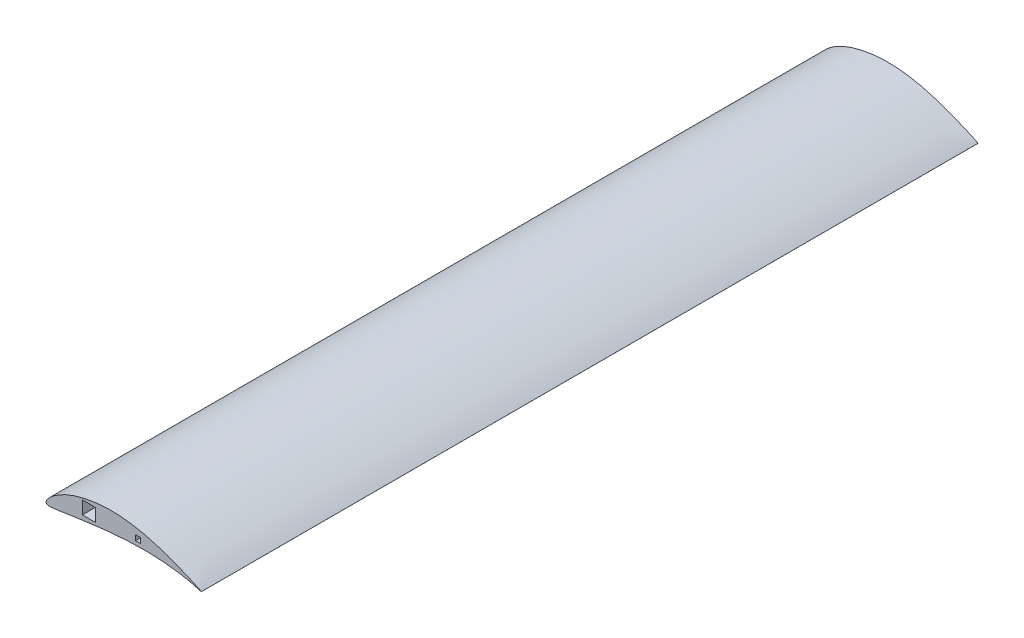
SolidWorks part; units mm, degrees
ref_plane "Front Plane" through (0, 0, 0) normal (0, 0, 1) x (1, 0, 0)
ref_plane "Top Plane" through (0, 0, 0) normal (0, 1, 0) x (1, 0, 0)
ref_plane "Right Plane" through (0, 0, 0) normal (1, 0, 0) x (0, 0, -1)
curve "Curve1"
  spline degree 3 poles (1.0002, -0.0023, 0) (1, 0, 0) (1.0002, 0.0023, 0) (0.9919, 0.0001, 0) (0.9849, 0.0027, 0) (0.9729, 0.003, 0) (0.9609, 0.0043, 0) (0.9483, 0.0054, 0) (0.9357, 0.0065, 0) (0.9231, 0.0077, 0) (0.9104, 0.0088, 0) (0.8978, 0.01, 0) (0.8852, 0.0111, 0) (0.8725, 0.0123, 0) (0.8599, 0.0134, 0) (0.8473, 0.0146, 0) (0.8347, 0.0157, 0) (0.8221, 0.0168, 0) (0.8094, 0.0179, 0) (0.7968, 0.019, 0) (0.7842, 0.0201, 0) (0.7716, 0.0211, 0) (0.759, 0.0222, 0) (0.7464, 0.0232, 0) (0.7337, 0.0243, 0) (0.7211, 0.0253, 0) (0.7085, 0.0263, 0) (0.6959, 0.0273, 0) (0.6833, 0.0283, 0) (0.6706, 0.0293, 0) (0.658, 0.0303, 0) (0.6454, 0.0313, 0) (0.6328, 0.0322, 0) (0.6202, 0.0331, 0) (0.6076, 0.0341, 0) (0.595, 0.035, 0) (0.5823, 0.0358, 0) (0.5697, 0.0367, 0) (0.5571, 0.0375, 0) (0.5446, 0.0384, 0) (0.532, 0.0392, 0) (0.5194, 0.0399, 0) (0.5068, 0.0407, 0) (0.4942, 0.0414, 0) (0.4816, 0.0421, 0) (0.469, 0.0427, 0) (0.4565, 0.0434, 0) (0.4439, 0.044, 0) (0.4313, 0.0445, 0) (0.4188, 0.0451, 0) (0.4062, 0.0456, 0) (0.3936, 0.046, 0) (0.3811, 0.0464, 0) (0.3685, 0.0468, 0) (0.356, 0.0472, 0) (0.3435, 0.0475, 0) (0.3309, 0.0477, 0) (0.3184, 0.0479, 0) (0.3059, 0.0481, 0) (0.2934, 0.0482, 0) (0.2809, 0.0482, 0) (0.2685, 0.0482, 0) (0.256, 0.0481, 0) (0.2436, 0.0479, 0) (0.2312, 0.0477, 0) (0.2189, 0.0474, 0) (0.2065, 0.047, 0) (0.1942, 0.0465, 0) (0.182, 0.0459, 0) (0.1698, 0.0452, 0) (0.1576, 0.0444, 0) (0.1456, 0.0434, 0) (0.1336, 0.0423, 0) (0.1217, 0.0411, 0) (0.1099, 0.0397, 0) (0.0983, 0.038, 0) (0.0868, 0.0362, 0) (0.0756, 0.0342, 0) (0.0647, 0.0319, 0) (0.0541, 0.0294, 0) (0.0441, 0.0266, 0) (0.0348, 0.0236, 0) (0.0266, 0.0205, 0) (0.0197, 0.0175, 0) (0.0142, 0.0146, 0) (0.0101, 0.012, 0) (0.007, 0.0098, 0) (0.0047, 0.0078, 0) (0.003, 0.006, 0) (0.0018, 0.0045, 0) (0.0009, 0.003, 0) (0.0003, 0.0017, 0) (0, 0.0004, 0) (0, -0.0008, 0) (0.0005, -0.0021, 0) (0.0015, -0.0032, 0) (0.0028, -0.0043, 0) (0.0046, -0.0054, 0) (0.0068, -0.0066, 0) (0.0097, -0.0078, 0) (0.0135, -0.0091, 0) (0.0186, -0.0106, 0) (0.0252, -0.0121, 0) (0.0334, -0.0135, 0) (0.043, -0.0148, 0) (0.0536, -0.0159, 0) (0.0648, -0.0167, 0) (0.0764, -0.0173, 0) (0.0882, -0.0177, 0) (0.1003, -0.018, 0) (0.1125, -0.0182, 0) (0.1247, -0.0183, 0) (0.1371, -0.0183, 0) (0.1495, -0.0182, 0) (0.162, -0.0181, 0) (0.1745, -0.0179, 0) (0.187, -0.0176, 0) (0.1996, -0.0174, 0) (0.2122, -0.0171, 0) (0.2248, -0.0167, 0) (0.2375, -0.0164, 0) (0.2501, -0.016, 0) (0.2628, -0.0156, 0) (0.2755, -0.0152, 0) (0.2882, -0.0147, 0) (0.3009, -0.0143, 0) (0.3136, -0.0139, 0) (0.3263, -0.0134, 0) (0.339, -0.0129, 0) (0.3517, -0.0125, 0) (0.3644, -0.012, 0) (0.3771, -0.0116, 0) (0.3897, -0.0111, 0) (0.4024, -0.0106, 0) (0.4151, -0.0102, 0) (0.4277, -0.0098, 0) (0.4404, -0.0093, 0) (0.4531, -0.0089, 0) (0.4657, -0.0085, 0) (0.4784, -0.0081, 0) (0.4911, -0.0077, 0) (0.5037, -0.0073, 0) (0.5164, -0.0069, 0) (0.5291, -0.0066, 0) (0.5417, -0.0062, 0) (0.5544, -0.0059, 0) (0.5671, -0.0055, 0) (0.5798, -0.0052, 0) (0.5924, -0.0049, 0) (0.6051, -0.0046, 0) (0.6178, -0.0044, 0) (0.6304, -0.0041, 0) (0.6431, -0.0039, 0) (0.6558, -0.0036, 0) (0.6685, -0.0034, 0) (0.6811, -0.0032, 0) (0.6938, -0.003, 0) (0.7065, -0.0029, 0) (0.7192, -0.0027, 0) (0.7318, -0.0026, 0) (0.7445, -0.0024, 0) (0.7572, -0.0023, 0) (0.7699, -0.0022, 0) (0.7826, -0.0021, 0) (0.7953, -0.002, 0) (0.8079, -0.0019, 0) (0.8206, -0.0019, 0) (0.8333, -0.0018, 0) (0.846, -0.0017, 0) (0.8588, -0.0017, 0) (0.8715, -0.0016, 0) (0.8842, -0.0015, 0) (0.8969, -0.0015, 0) (0.9096, -0.0014, 0) (0.9223, -0.0013, 0) (0.935, -0.0012, 0) (0.9477, -0.0011, 0) (0.9604, -0.0011, 0) (0.9725, -0.0007, 0) (0.9848, -0.0014, 0) (0.9918, 0.0007, 0) (1.0002, -0.0023, 0) (1, 0, 0) (1.0002, 0.0023, 0) knots -0.007874 -0.002894 -0.000332 0 0.000332 0.002885 0.007815 0.013623 0.01978 0.026037 0.032316 0.038604 0.044895 0.051184 0.057469 0.06375 0.070028 0.076304 0.082578 0.088851 0.095124 0.101396 0.107668 0.113941 0.120213 0.126487 0.132762 0.139036 0.145311 0.151585 0.157859 0.16413 0.170401 0.17667 0.182937 0.189202 0.195466 0.201728 0.207987 0.214245 0.2205 0.226754 0.233005 0.239253 0.2455 0.251744 0.257986 0.264226 0.270464 0.2767 0.282933 0.289165 0.295394 0.30162 0.307843 0.314063 0.32028 0.326491 0.332699 0.3389 0.345096 0.351285 0.357467 0.363641 0.369805 0.375959 0.382101 0.38823 0.394345 0.400443 0.406521 0.412577 0.418607 0.424607 0.430573 0.436498 0.442374 0.448192 0.453938 0.459595 0.465142 0.470542 0.475738 0.480625 0.48504 0.488808 0.491844 0.494208 0.496047 0.497501 0.498679 0.499657 0.500486 0.501199 0.501823 0.502412 0.503041 0.50376 0.504602 0.505602 0.50682 0.508337 0.510284 0.512841 0.516185 0.520365 0.525232 0.530552 0.536146 0.541914 0.547804 0.553781 0.559821 0.565909 0.57203 0.578179 0.584352 0.590546 0.596759 0.60299 0.609237 0.615497 0.621768 0.62805 0.634339 0.640634 0.646932 0.653231 0.659529 0.665824 0.672115 0.678404 0.684692 0.690977 0.69726 0.703542 0.709822 0.716099 0.722375 0.728651 0.734927 0.741206 0.747487 0.753768 0.76005 0.766331 0.772611 0.778892 0.785172 0.791451 0.79773 0.804009 0.810289 0.816569 0.822848 0.829126 0.835406 0.841685 0.847965 0.854245 0.860527 0.866808 0.87309 0.879373 0.885657 0.891942 0.898228 0.904515 0.910804 0.917095 0.923389 0.929686 0.935986 0.942288 0.948588 0.954885 0.961183 0.96748 0.973774 0.980051 0.986247 0.992126 0.997106 0.999668 1 1.000332 1.002885 1.007815 periodic
curve "Curve6"
  spline degree 3 poles (0, 0, 0) (0.0002, 0.0017, 0) (0.0007, 0.0052, 0) (0.0046, 0.01, 0) (0.01, 0.0151, 0) (0.0174, 0.0207, 0) (0.027, 0.0264, 0) (0.0385, 0.0321, 0) (0.052, 0.0379, 0) (0.0675, 0.0434, 0) (0.0847, 0.0488, 0) (0.1038, 0.0538, 0) (0.1245, 0.0586, 0) (0.1469, 0.063, 0) (0.1707, 0.0671, 0) (0.196, 0.0706, 0) (0.2226, 0.0737, 0) (0.2503, 0.0762, 0) (0.2792, 0.0783, 0) (0.3089, 0.0796, 0) (0.3395, 0.0805, 0) (0.3708, 0.0807, 0) (0.4026, 0.0805, 0) (0.4348, 0.0796, 0) (0.4674, 0.0782, 0) (0.5, 0.0763, 0) (0.5327, 0.074, 0) (0.5652, 0.0714, 0) (0.5974, 0.0683, 0) (0.6292, 0.0649, 0) (0.6605, 0.0611, 0) (0.6911, 0.057, 0) (0.7209, 0.0527, 0) (0.7497, 0.0482, 0) (0.7774, 0.0435, 0) (0.804, 0.0388, 0) (0.8292, 0.0342, 0) (0.8531, 0.0298, 0) (0.8754, 0.0255, 0) (0.8961, 0.0215, 0) (0.9151, 0.0177, 0) (0.9324, 0.0142, 0) (0.9478, 0.0111, 0) (0.9613, 0.0083, 0) (0.9728, 0.0059, 0) (0.9823, 0.0039, 0) (0.9897, 0.0023, 0) (0.9949, 0.0006, 0) (0.9983, 0.0007, 0) (0.9996, 0.0001, 0) (1, 0, 0) knots 0 0 0 0 0.004816 0.010311 0.017533 0.026619 0.037456 0.050036 0.064348 0.080358 0.098009 0.117234 0.138018 0.160262 0.183891 0.2088 0.234911 0.262128 0.290345 0.319442 0.34932 0.379858 0.410934 0.442439 0.474224 0.506171 0.538142 0.570006 0.601639 0.632894 0.663653 0.693783 0.723155 0.751647 0.779129 0.805464 0.830536 0.854232 0.876442 0.897072 0.916014 0.933209 0.948567 0.962012 0.9735 0.982962 0.990398 0.99574 0.998893 1 1 1 1
curve "Curve7"
  spline degree 3 poles (0.0009, -0.0041, 0) (-0.0004, 0.0004, 0) (0.0009, 0.0052, 0) (0.0045, 0.01, 0) (0.01, 0.0151, 0) (0.0174, 0.0207, 0) (0.027, 0.0264, 0) (0.0385, 0.0321, 0) (0.052, 0.0379, 0) (0.0675, 0.0434, 0) (0.0847, 0.0488, 0) (0.1038, 0.0538, 0) (0.1245, 0.0586, 0) (0.1469, 0.063, 0) (0.1707, 0.0671, 0) (0.196, 0.0706, 0) (0.2226, 0.0737, 0) (0.2503, 0.0762, 0) (0.2792, 0.0783, 0) (0.3089, 0.0796, 0) (0.3395, 0.0805, 0) (0.3708, 0.0807, 0) (0.4026, 0.0805, 0) (0.4348, 0.0796, 0) (0.4674, 0.0782, 0) (0.5, 0.0763, 0) (0.5327, 0.074, 0) (0.5652, 0.0714, 0) (0.5974, 0.0683, 0) (0.6292, 0.0649, 0) (0.6605, 0.0611, 0) (0.6911, 0.057, 0) (0.7209, 0.0527, 0) (0.7497, 0.0482, 0) (0.7774, 0.0435, 0) (0.804, 0.0388, 0) (0.8292, 0.0342, 0) (0.8531, 0.0298, 0) (0.8754, 0.0255, 0) (0.8961, 0.0215, 0) (0.9151, 0.0177, 0) (0.9324, 0.0142, 0) (0.9478, 0.0111, 0) (0.9613, 0.0083, 0) (0.9728, 0.0059, 0) (0.9823, 0.0038, 0) (0.9896, 0.0024, 0) (0.9953, 0.0005, 0) (0.9978, 0.0008, 0) (1.0006, -0.0001, 0) (0.9977, 0.0003, 0) (0.9953, 0, 0) (0.9896, 0.0009, 0) (0.9823, 0.0014, 0) (0.9728, 0.0025, 0) (0.9613, 0.0036, 0) (0.9478, 0.0048, 0) (0.9324, 0.006, 0) (0.9151, 0.0072, 0) (0.8961, 0.0083, 0) (0.8754, 0.0093, 0) (0.8531, 0.0102, 0) (0.8292, 0.0108, 0) (0.8039, 0.0112, 0) (0.7774, 0.0112, 0) (0.7496, 0.0109, 0) (0.7208, 0.0102, 0) (0.6911, 0.0092, 0) (0.6605, 0.0079, 0) (0.6292, 0.0062, 0) (0.5974, 0.004, 0) (0.5652, 0.0016, 0) (0.5326, -0.0011, 0) (0.5, -0.0039, 0) (0.4673, -0.0069, 0) (0.4348, -0.0098, 0) (0.4026, -0.0128, 0) (0.3708, -0.0154, 0) (0.3395, -0.018, 0) (0.3089, -0.0201, 0) (0.2792, -0.022, 0) (0.2504, -0.0233, 0) (0.2226, -0.0244, 0) (0.1961, -0.0249, 0) (0.1708, -0.0253, 0) (0.147, -0.0252, 0) (0.1246, -0.0248, 0) (0.1039, -0.024, 0) (0.0848, -0.023, 0) (0.0676, -0.0217, 0) (0.0522, -0.0201, 0) (0.0387, -0.0182, 0) (0.0271, -0.0161, 0) (0.0176, -0.0135, 0) (0.01, -0.0109, 0) (0.0046, -0.0077, 0) (0.0009, -0.0041, 0) (-0.0004, 0.0004, 0) (0.0009, 0.0052, 0) knots -0.007287 -0.004212 -0.00188 0 0.002428 0.005198 0.00884 0.013421 0.018885 0.025227 0.032443 0.040515 0.049414 0.059107 0.069586 0.080801 0.092714 0.105273 0.118437 0.13216 0.146386 0.161056 0.17612 0.191517 0.207184 0.223068 0.239094 0.255201 0.27132 0.287385 0.303334 0.319092 0.3346 0.349791 0.364599 0.378965 0.392821 0.406098 0.418739 0.430686 0.441884 0.452285 0.461835 0.470504 0.478247 0.485026 0.490819 0.495589 0.499338 0.502031 0.503621 0.504179 0.504707 0.506286 0.508919 0.512589 0.517281 0.522978 0.529643 0.537254 0.545772 0.555157 0.565377 0.576386 0.588132 0.60057 0.613645 0.627312 0.641507 0.656169 0.671241 0.686661 0.702362 0.718285 0.734352 0.750492 0.766637 0.782713 0.798656 0.81438 0.829825 0.844919 0.8596 0.873808 0.887483 0.900562 0.912999 0.924742 0.935744 0.94596 0.955342 0.963865 0.971494 0.978201 0.983972 0.988807 0.992713 0.995788 0.99812 1 1.002428 1.005198 1.00884 periodic
curve "Curve8"
  spline degree 3 poles (1, 0.0001, 0) (0.9992, 0.0006, 0) (0.9962, 0.0026, 0) (0.9897, 0.0065, 0) (0.9795, 0.0117, 0) (0.966, 0.0177, 0) (0.9494, 0.025, 0) (0.9297, 0.0336, 0) (0.9068, 0.0433, 0) (0.8812, 0.0541, 0) (0.853, 0.0656, 0) (0.8225, 0.0776, 0) (0.79, 0.0897, 0) (0.7558, 0.1017, 0) (0.7202, 0.1132, 0) (0.6835, 0.1241, 0) (0.6459, 0.134, 0) (0.6078, 0.1427, 0) (0.5695, 0.1499, 0) (0.5311, 0.1556, 0) (0.4927, 0.1597, 0) (0.4545, 0.162, 0) (0.4165, 0.1627, 0) (0.3791, 0.1616, 0) (0.3423, 0.1589, 0) (0.3063, 0.1546, 0) (0.2715, 0.1489, 0) (0.2379, 0.1418, 0) (0.2058, 0.1335, 0) (0.1754, 0.124, 0) (0.1469, 0.1134, 0) (0.1204, 0.1018, 0) (0.0962, 0.0895, 0) (0.0744, 0.0767, 0) (0.0552, 0.0638, 0) (0.0386, 0.051, 0) (0.0247, 0.0387, 0) (0.0137, 0.027, 0) (0.0057, 0.0163, 0) (0.0011, 0.0075, 0) (-0.0003, 0.0005, 0) (0.0007, -0.0053, 0) (0.0058, -0.01, 0) (0.0142, -0.0123, 0) (0.0253, -0.0129, 0) (0.0391, -0.0122, 0) (0.0556, -0.0102, 0) (0.0748, -0.0075, 0) (0.0966, -0.0042, 0) (0.1207, -0.0007, 0) (0.1472, 0.0033, 0) (0.1757, 0.0076, 0) (0.206, 0.0121, 0) (0.2381, 0.0168, 0) (0.2716, 0.0215, 0) (0.3064, 0.0261, 0) (0.3423, 0.0305, 0) (0.3791, 0.0347, 0) (0.4165, 0.0385, 0) (0.4544, 0.0419, 0) (0.4926, 0.0448, 0) (0.531, 0.047, 0) (0.5694, 0.0486, 0) (0.6077, 0.0495, 0) (0.6458, 0.0495, 0) (0.6833, 0.0486, 0) (0.7201, 0.0469, 0) (0.7557, 0.0444, 0) (0.7899, 0.0412, 0) (0.8225, 0.0376, 0) (0.853, 0.0334, 0) (0.8812, 0.0289, 0) (0.9069, 0.0241, 0) (0.9297, 0.0193, 0) (0.9494, 0.0145, 0) (0.966, 0.0098, 0) (0.9793, 0.0054, 0) (0.9895, 0.0024, 0) (0.9961, 0.0007, 0) (0.9992, 0.0001, 0) (1, -0.0001, 0) knots 0 0 0 0 0.001413 0.005226 0.010781 0.017816 0.026461 0.036791 0.048686 0.062017 0.076639 0.092363 0.109003 0.126387 0.144339 0.162701 0.181313 0.200023 0.218713 0.237261 0.255692 0.274037 0.292193 0.310133 0.327788 0.345097 0.362002 0.378421 0.394287 0.409543 0.424114 0.437938 0.450942 0.463044 0.474154 0.484165 0.493024 0.500713 0.507126 0.51213 0.514904 0.517171 0.520262 0.524245 0.529498 0.536092 0.544061 0.553363 0.563905 0.575615 0.58842 0.602227 0.616944 0.632457 0.648676 0.665501 0.682818 0.700538 0.718564 0.736789 0.755151 0.773513 0.791878 0.810245 0.828489 0.846493 0.864125 0.881249 0.897725 0.913415 0.928184 0.941897 0.954411 0.965603 0.97535 0.983576 0.990285 0.995433 0.9988 1 1 1 1
sketch "Sketch3" plane through (0, 0, 0) normal (0, 0, 1) x (1, 0, 0)
  line L0 (0, 0) -> (50, 0) construction
  line L1 (0.2298, 0.0405) -> (0.2298, 0.0158) construction
  line L2 (0.1804, 0.0405) -> (0.2298, 0.0405)
  line L3 (0.1804, 0.0405) -> (0.1804, -0.0089)
  line L4 (0.1804, -0.0089) -> (0.2298, -0.0089)
  line L5 (0.2298, 0.0405) -> (0.2298, -0.0089)
  line L6 (0.4642, 0.0242) -> (0.4889, 0.0242)
  line L7 (0.4642, 0.0242) -> (0.4642, -0.0005)
  line L8 (0.4642, -0.0005) -> (0.4889, -0.0005)
  line L9 (0.4889, 0.0242) -> (0.4889, -0.0005)
  line L10 (0.2298, 0.0158) -> (0.2146, 0.0158) construction
  line L11 (0.2146, 0.0158) -> (0.2146, 0.0405) construction
  line L12 (0.2146, 0.0405) -> (0.2298, 0.0405) construction
  line L13 (0, 0) -> (500, 0) construction
  line L14 (0.1804, 0.0458) -> (0.1804, -0.0178) construction
  line L15 (0, 0) -> (0, -165.9812) construction
  line L16 (0, -165.9812) -> (300, -165.9812) construction
  line L17 (72.7802, 36.2202) -> (92.7802, 36.2202) construction
  line L18 (70.2802, 13.7202) -> (95.2802, 13.7202)
  line L19 (70.2802, 13.7202) -> (70.2802, 38.7202)
  line L20 (70.2802, 38.7202) -> (95.2802, 38.7202)
  line L21 (95.2802, 13.7202) -> (95.2802, 38.7202)
  line L22 (92.7802, 16.2202) -> (92.7802, 36.2202) construction
  line L23 (72.7802, 16.2202) -> (92.7802, 16.2202) construction
  line L24 (72.7802, 16.2202) -> (72.7802, 36.2202) construction
  line L25 (300, -0.018) -> (300, 0.015)
  line L26 (172.9506, 31.8748) -> (182.9506, 31.8748)
  line L27 (172.9506, 31.8748) -> (172.9506, 21.8748)
  line L28 (172.9506, 21.8748) -> (182.9506, 21.8748)
  line L29 (182.9506, 31.8748) -> (182.9506, 21.8748)
  spline S0 degree 3 poles (1.0002, -0.0023) (1, 0) (1.0002, 0.0023) (0.9919, 0.0001) (0.9849, 0.0027) (0.9729, 0.003) (0.9609, 0.0043) (0.9483, 0.0054) (0.9357, 0.0065) (0.9231, 0.0077) (0.9104, 0.0088) (0.8978, 0.01) (0.8852, 0.0111) (0.8725, 0.0123) (0.8599, 0.0134) (0.8473, 0.0146) (0.8347, 0.0157) (0.8221, 0.0168) (0.8094, 0.0179) (0.7968, 0.019) (0.7842, 0.0201) (0.7716, 0.0211) (0.759, 0.0222) (0.7464, 0.0232) (0.7337, 0.0243) (0.7211, 0.0253) (0.7085, 0.0263) (0.6959, 0.0273) (0.6833, 0.0283) (0.6706, 0.0293) (0.658, 0.0303) (0.6454, 0.0313) (0.6328, 0.0322) (0.6202, 0.0331) (0.6076, 0.0341) (0.595, 0.035) (0.5823, 0.0358) (0.5697, 0.0367) (0.5571, 0.0375) (0.5446, 0.0384) (0.532, 0.0392) (0.5194, 0.0399) (0.5068, 0.0407) (0.4942, 0.0414) (0.4816, 0.0421) (0.469, 0.0427) (0.4565, 0.0434) (0.4439, 0.044) (0.4313, 0.0445) (0.4188, 0.0451) (0.4062, 0.0456) (0.3936, 0.046) (0.3811, 0.0464) (0.3685, 0.0468) (0.356, 0.0472) (0.3435, 0.0475) (0.3309, 0.0477) (0.3184, 0.0479) (0.3059, 0.0481) (0.2934, 0.0482) (0.2809, 0.0482) (0.2685, 0.0482) (0.256, 0.0481) (0.2436, 0.0479) (0.2312, 0.0477) (0.2189, 0.0474) (0.2065, 0.047) (0.1942, 0.0465) (0.182, 0.0459) (0.1698, 0.0452) (0.1576, 0.0444) (0.1456, 0.0434) (0.1336, 0.0423) (0.1217, 0.0411) (0.1099, 0.0397) (0.0983, 0.038) (0.0868, 0.0362) (0.0756, 0.0342) (0.0647, 0.0319) (0.0541, 0.0294) (0.0441, 0.0266) (0.0348, 0.0236) (0.0266, 0.0205) (0.0197, 0.0175) (0.0142, 0.0146) (0.0101, 0.012) (0.007, 0.0098) (0.0047, 0.0078) (0.003, 0.006) (0.0018, 0.0045) (0.0009, 0.003) (0.0003, 0.0017) (0, 0.0004) (0, -0.0008) (0.0005, -0.0021) (0.0015, -0.0032) (0.0028, -0.0043) (0.0046, -0.0054) (0.0068, -0.0066) (0.0097, -0.0078) (0.0135, -0.0091) (0.0186, -0.0106) (0.0252, -0.0121) (0.0334, -0.0135) (0.043, -0.0148) (0.0536, -0.0159) (0.0648, -0.0167) (0.0764, -0.0173) (0.0882, -0.0177) (0.1003, -0.018) (0.1125, -0.0182) (0.1247, -0.0183) (0.1371, -0.0183) (0.1495, -0.0182) (0.162, -0.0181) (0.1745, -0.0179) (0.187, -0.0176) (0.1996, -0.0174) (0.2122, -0.0171) (0.2248, -0.0167) (0.2375, -0.0164) (0.2501, -0.016) (0.2628, -0.0156) (0.2755, -0.0152) (0.2882, -0.0147) (0.3009, -0.0143) (0.3136, -0.0139) (0.3263, -0.0134) (0.339, -0.0129) (0.3517, -0.0125) (0.3644, -0.012) (0.3771, -0.0116) (0.3897, -0.0111) (0.4024, -0.0106) (0.4151, -0.0102) (0.4277, -0.0098) (0.4404, -0.0093) (0.4531, -0.0089) (0.4657, -0.0085) (0.4784, -0.0081) (0.4911, -0.0077) (0.5037, -0.0073) (0.5164, -0.0069) (0.5291, -0.0066) (0.5417, -0.0062) (0.5544, -0.0059) (0.5671, -0.0055) (0.5798, -0.0052) (0.5924, -0.0049) (0.6051, -0.0046) (0.6178, -0.0044) (0.6304, -0.0041) (0.6431, -0.0039) (0.6558, -0.0036) (0.6685, -0.0034) (0.6811, -0.0032) (0.6938, -0.003) (0.7065, -0.0029) (0.7192, -0.0027) (0.7318, -0.0026) (0.7445, -0.0024) (0.7572, -0.0023) (0.7699, -0.0022) (0.7826, -0.0021) (0.7953, -0.002) (0.8079, -0.0019) (0.8206, -0.0019) (0.8333, -0.0018) (0.846, -0.0017) (0.8588, -0.0017) (0.8715, -0.0016) (0.8842, -0.0015) (0.8969, -0.0015) (0.9096, -0.0014) (0.9223, -0.0013) (0.935, -0.0012) (0.9477, -0.0011) (0.9604, -0.0011) (0.9725, -0.0007) (0.9848, -0.0014) (0.9918, 0.0007) (1.0002, -0.0023) (1, 0) (1.0002, 0.0023) knots -0.007874 -0.002894 -0.000332 0 0.000332 0.002885 0.007815 0.013623 0.01978 0.026037 0.032316 0.038604 0.044895 0.051184 0.057469 0.06375 0.070028 0.076304 0.082578 0.088851 0.095124 0.101396 0.107668 0.113941 0.120213 0.126487 0.132762 0.139036 0.145311 0.151585 0.157859 0.16413 0.170401 0.17667 0.182937 0.189202 0.195466 0.201728 0.207987 0.214245 0.2205 0.226754 0.233005 0.239253 0.2455 0.251744 0.257986 0.264226 0.270464 0.2767 0.282933 0.289165 0.295394 0.30162 0.307843 0.314063 0.32028 0.326491 0.332699 0.3389 0.345096 0.351285 0.357467 0.363641 0.369805 0.375959 0.382101 0.38823 0.394345 0.400443 0.406521 0.412577 0.418607 0.424607 0.430573 0.436498 0.442374 0.448192 0.453938 0.459595 0.465142 0.470542 0.475738 0.480625 0.48504 0.488808 0.491844 0.494208 0.496047 0.497501 0.498679 0.499657 0.500486 0.501199 0.501823 0.502412 0.503041 0.50376 0.504602 0.505602 0.50682 0.508337 0.510284 0.512841 0.516185 0.520365 0.525232 0.530552 0.536146 0.541914 0.547804 0.553781 0.559821 0.565909 0.57203 0.578179 0.584352 0.590546 0.596759 0.60299 0.609237 0.615497 0.621768 0.62805 0.634339 0.640634 0.646932 0.653231 0.659529 0.665824 0.672115 0.678404 0.684692 0.690977 0.69726 0.703542 0.709822 0.716099 0.722375 0.728651 0.734927 0.741206 0.747487 0.753768 0.76005 0.766331 0.772611 0.778892 0.785172 0.791451 0.79773 0.804009 0.810289 0.816569 0.822848 0.829126 0.835406 0.841685 0.847965 0.854245 0.860527 0.866808 0.87309 0.879373 0.885657 0.891942 0.898228 0.904515 0.910804 0.917095 0.923389 0.929686 0.935986 0.942288 0.948588 0.954885 0.961183 0.96748 0.973774 0.980051 0.986247 0.992126 0.997106 0.999668 1 1.000332 1.002885 1.007815 only from (1, 0) to (1, 0) construction
  spline S1 degree 3 poles (1.0002, -0.0023) (1, 0) (1.0002, 0.0023) (0.9919, 0.0001) (0.9849, 0.0027) (0.9729, 0.003) (0.9609, 0.0043) (0.9483, 0.0054) (0.9357, 0.0065) (0.9231, 0.0077) (0.9104, 0.0088) (0.8978, 0.01) (0.8852, 0.0111) (0.8725, 0.0123) (0.8599, 0.0134) (0.8473, 0.0146) (0.8347, 0.0157) (0.8221, 0.0168) (0.8094, 0.0179) (0.7968, 0.019) (0.7842, 0.0201) (0.7716, 0.0211) (0.759, 0.0222) (0.7464, 0.0232) (0.7337, 0.0243) (0.7211, 0.0253) (0.7085, 0.0263) (0.6959, 0.0273) (0.6833, 0.0283) (0.6706, 0.0293) (0.658, 0.0303) (0.6454, 0.0313) (0.6328, 0.0322) (0.6202, 0.0331) (0.6076, 0.0341) (0.595, 0.035) (0.5823, 0.0358) (0.5697, 0.0367) (0.5571, 0.0375) (0.5446, 0.0384) (0.532, 0.0392) (0.5194, 0.0399) (0.5068, 0.0407) (0.4942, 0.0414) (0.4816, 0.0421) (0.469, 0.0427) (0.4565, 0.0434) (0.4439, 0.044) (0.4313, 0.0445) (0.4188, 0.0451) (0.4062, 0.0456) (0.3936, 0.046) (0.3811, 0.0464) (0.3685, 0.0468) (0.356, 0.0472) (0.3435, 0.0475) (0.3309, 0.0477) (0.3184, 0.0479) (0.3059, 0.0481) (0.2934, 0.0482) (0.2809, 0.0482) (0.2685, 0.0482) (0.256, 0.0481) (0.2436, 0.0479) (0.2312, 0.0477) (0.2189, 0.0474) (0.2065, 0.047) (0.1942, 0.0465) (0.182, 0.0459) (0.1698, 0.0452) (0.1576, 0.0444) (0.1456, 0.0434) (0.1336, 0.0423) (0.1217, 0.0411) (0.1099, 0.0397) (0.0983, 0.038) (0.0868, 0.0362) (0.0756, 0.0342) (0.0647, 0.0319) (0.0541, 0.0294) (0.0441, 0.0266) (0.0348, 0.0236) (0.0266, 0.0205) (0.0197, 0.0175) (0.0142, 0.0146) (0.0101, 0.012) (0.007, 0.0098) (0.0047, 0.0078) (0.003, 0.006) (0.0018, 0.0045) (0.0009, 0.003) (0.0003, 0.0017) (0, 0.0004) (0, -0.0008) (0.0005, -0.0021) (0.0015, -0.0032) (0.0028, -0.0043) (0.0046, -0.0054) (0.0068, -0.0066) (0.0097, -0.0078) (0.0135, -0.0091) (0.0186, -0.0106) (0.0252, -0.0121) (0.0334, -0.0135) (0.043, -0.0148) (0.0536, -0.0159) (0.0648, -0.0167) (0.0764, -0.0173) (0.0882, -0.0177) (0.1003, -0.018) (0.1125, -0.0182) (0.1247, -0.0183) (0.1371, -0.0183) (0.1495, -0.0182) (0.162, -0.0181) (0.1745, -0.0179) (0.187, -0.0176) (0.1996, -0.0174) (0.2122, -0.0171) (0.2248, -0.0167) (0.2375, -0.0164) (0.2501, -0.016) (0.2628, -0.0156) (0.2755, -0.0152) (0.2882, -0.0147) (0.3009, -0.0143) (0.3136, -0.0139) (0.3263, -0.0134) (0.339, -0.0129) (0.3517, -0.0125) (0.3644, -0.012) (0.3771, -0.0116) (0.3897, -0.0111) (0.4024, -0.0106) (0.4151, -0.0102) (0.4277, -0.0098) (0.4404, -0.0093) (0.4531, -0.0089) (0.4657, -0.0085) (0.4784, -0.0081) (0.4911, -0.0077) (0.5037, -0.0073) (0.5164, -0.0069) (0.5291, -0.0066) (0.5417, -0.0062) (0.5544, -0.0059) (0.5671, -0.0055) (0.5798, -0.0052) (0.5924, -0.0049) (0.6051, -0.0046) (0.6178, -0.0044) (0.6304, -0.0041) (0.6431, -0.0039) (0.6558, -0.0036) (0.6685, -0.0034) (0.6811, -0.0032) (0.6938, -0.003) (0.7065, -0.0029) (0.7192, -0.0027) (0.7318, -0.0026) (0.7445, -0.0024) (0.7572, -0.0023) (0.7699, -0.0022) (0.7826, -0.0021) (0.7953, -0.002) (0.8079, -0.0019) (0.8206, -0.0019) (0.8333, -0.0018) (0.846, -0.0017) (0.8588, -0.0017) (0.8715, -0.0016) (0.8842, -0.0015) (0.8969, -0.0015) (0.9096, -0.0014) (0.9223, -0.0013) (0.935, -0.0012) (0.9477, -0.0011) (0.9604, -0.0011) (0.9725, -0.0007) (0.9848, -0.0014) (0.9918, 0.0007) (1.0002, -0.0023) (1, 0) (1.0002, 0.0023) knots -0.007874 -0.002894 -0.000332 0 0.000332 0.002885 0.007815 0.013623 0.01978 0.026037 0.032316 0.038604 0.044895 0.051184 0.057469 0.06375 0.070028 0.076304 0.082578 0.088851 0.095124 0.101396 0.107668 0.113941 0.120213 0.126487 0.132762 0.139036 0.145311 0.151585 0.157859 0.16413 0.170401 0.17667 0.182937 0.189202 0.195466 0.201728 0.207987 0.214245 0.2205 0.226754 0.233005 0.239253 0.2455 0.251744 0.257986 0.264226 0.270464 0.2767 0.282933 0.289165 0.295394 0.30162 0.307843 0.314063 0.32028 0.326491 0.332699 0.3389 0.345096 0.351285 0.357467 0.363641 0.369805 0.375959 0.382101 0.38823 0.394345 0.400443 0.406521 0.412577 0.418607 0.424607 0.430573 0.436498 0.442374 0.448192 0.453938 0.459595 0.465142 0.470542 0.475738 0.480625 0.48504 0.488808 0.491844 0.494208 0.496047 0.497501 0.498679 0.499657 0.500486 0.501199 0.501823 0.502412 0.503041 0.50376 0.504602 0.505602 0.50682 0.508337 0.510284 0.512841 0.516185 0.520365 0.525232 0.530552 0.536146 0.541914 0.547804 0.553781 0.559821 0.565909 0.57203 0.578179 0.584352 0.590546 0.596759 0.60299 0.609237 0.615497 0.621768 0.62805 0.634339 0.640634 0.646932 0.653231 0.659529 0.665824 0.672115 0.678404 0.684692 0.690977 0.69726 0.703542 0.709822 0.716099 0.722375 0.728651 0.734927 0.741206 0.747487 0.753768 0.76005 0.766331 0.772611 0.778892 0.785172 0.791451 0.79773 0.804009 0.810289 0.816569 0.822848 0.829126 0.835406 0.841685 0.847965 0.854245 0.860527 0.866808 0.87309 0.879373 0.885657 0.891942 0.898228 0.904515 0.910804 0.917095 0.923389 0.929686 0.935986 0.942288 0.948588 0.954885 0.961183 0.96748 0.973774 0.980051 0.986247 0.992126 0.997106 0.999668 1 1.000332 1.002885 1.007815 only from (1, 0) to (1, 0) construction
  spline S2 degree 3 poles (500.0959, -1.1537) (499.9892, 0.0005) (500.0921, 1.1423) (495.9334, 0.0411) (492.471, 1.3334) (486.441, 1.5239) (480.4457, 2.1624) (474.1516, 2.6955) (467.853, 3.2724) (461.5326, 3.8433) (455.2123, 4.419) (448.8921, 4.9943) (442.5755, 5.5699) (436.262, 6.142) (429.9511, 6.7101) (423.6424, 7.2769) (417.3349, 7.8378) (411.0282, 8.3936) (404.7219, 8.9456) (398.4154, 9.4908) (392.1084, 10.0313) (385.8007, 10.567) (379.4922, 11.0968) (373.1826, 11.6221) (366.8717, 12.1412) (360.56, 12.6562) (354.2482, 13.167) (347.9364, 13.6717) (341.6252, 14.172) (335.3149, 14.6658) (329.0056, 15.1544) (322.6972, 15.6341) (316.3902, 16.1098) (310.0841, 16.5743) (303.7793, 17.0336) (297.4758, 17.4828) (291.1738, 17.9236) (284.8734, 18.3542) (278.5742, 18.7741) (272.2766, 19.1842) (265.9803, 19.5806) (259.6857, 19.9669) (253.3925, 20.3385) (247.1009, 20.6976) (240.8108, 21.0438) (234.5219, 21.3728) (228.2344, 21.6877) (221.9482, 21.986) (215.6634, 22.269) (209.38, 22.5336) (203.0985, 22.7823) (196.8192, 23.011) (190.5422, 23.2214) (184.2678, 23.4112) (177.9968, 23.5814) (171.7294, 23.7279) (165.4666, 23.8538) (159.2085, 23.9536) (152.9563, 24.0285) (146.7104, 24.0763) (140.4718, 24.0951) (134.2418, 24.0833) (128.0212, 24.0398) (121.8114, 23.9589) (115.6139, 23.8431) (109.4305, 23.6857) (103.2636, 23.4864) (97.1155, 23.2386) (90.9895, 22.9417) (84.8889, 22.5902) (78.8182, 22.1795) (72.7826, 21.7035) (66.7884, 21.1583) (60.844, 20.5334) (54.9591, 19.8268) (49.1468, 19.0246) (43.424, 18.1218) (37.8124, 17.1067) (32.343, 15.9694) (27.0604, 14.7062) (22.0393, 13.3164) (17.395, 11.8221) (13.2795, 10.2688) (9.8299, 8.731) (7.0994, 7.2913) (5.0301, 6.0034) (3.4945, 4.8762) (2.3559, 3.8907) (1.5099, 3.0166) (0.8848, 2.2285) (0.4335, 1.5087) (0.1314, 0.8425) (-0.0182, 0.2062) (0.0104, -0.4232) (0.2632, -1.0376) (0.7397, -1.6094) (1.4111, -2.154) (2.2826, -2.7045) (3.4007, -3.2811) (4.8511, -3.898) (6.7651, -4.5654) (9.3055, -5.2886) (12.6143, -6.039) (16.7206, -6.7632) (21.5126, -7.4019) (26.7966, -7.9252) (32.394, -8.3361) (38.1897, -8.6462) (44.118, -8.8675) (50.1404, -9.0195) (56.2306, -9.1096) (62.3698, -9.1496) (68.5456, -9.1443) (74.75, -9.104) (80.9785, -9.0332) (87.2282, -8.9364) (93.4969, -8.818) (99.783, -8.6804) (106.0845, -8.5272) (112.3995, -8.3597) (118.7258, -8.1811) (125.0618, -7.9892) (131.4053, -7.7924) (137.7541, -7.5838) (144.1059, -7.37) (150.4584, -7.1501) (156.8097, -6.9267) (163.1584, -6.6992) (169.5042, -6.4709) (175.8475, -6.2404) (182.1887, -6.0105) (188.5278, -5.7806) (194.865, -5.5531) (201.2002, -5.325) (207.5338, -5.1031) (213.8656, -4.8806) (220.1961, -4.6635) (226.5264, -4.4495) (232.8578, -4.2412) (239.1911, -4.0373) (245.5262, -3.8375) (251.8626, -3.6436) (258.1993, -3.458) (264.5356, -3.2755) (270.8718, -3.1019) (277.2076, -2.9318) (283.5434, -2.7691) (289.8787, -2.6119) (296.2141, -2.4645) (302.5496, -2.3201) (308.8856, -2.184) (315.2216, -2.0569) (321.5574, -1.9335) (327.8933, -1.8191) (334.2294, -1.7131) (340.5661, -1.6125) (346.9033, -1.5208) (353.2413, -1.4364) (359.58, -1.3587) (365.9191, -1.2888) (372.2588, -1.223) (378.5993, -1.1661) (384.9408, -1.1114) (391.2835, -1.0632) (397.6273, -1.0167) (403.9727, -0.9749) (410.3197, -0.9366) (416.669, -0.8947) (423.021, -0.8606) (429.376, -0.8257) (435.7337, -0.7924) (442.0922, -0.7597) (448.4498, -0.726) (454.8061, -0.6894) (461.1609, -0.6473) (467.5175, -0.6036) (473.8564, -0.5446) (480.2008, -0.5303) (486.2618, -0.3697) (492.3763, -0.6848) (495.8827, 0.3278) (500.0959, -1.1537) (499.9892, 0.0005) (500.0921, 1.1423) knots -0.007874 -0.002894 -0.000332 0 0.000332 0.002885 0.007815 0.013623 0.01978 0.026037 0.032316 0.038604 0.044895 0.051184 0.057469 0.06375 0.070028 0.076304 0.082578 0.088851 0.095124 0.101396 0.107668 0.113941 0.120213 0.126487 0.132762 0.139036 0.145311 0.151585 0.157859 0.16413 0.170401 0.17667 0.182937 0.189202 0.195466 0.201728 0.207987 0.214245 0.2205 0.226754 0.233005 0.239253 0.2455 0.251744 0.257986 0.264226 0.270464 0.2767 0.282933 0.289165 0.295394 0.30162 0.307843 0.314063 0.32028 0.326491 0.332699 0.3389 0.345096 0.351285 0.357467 0.363641 0.369805 0.375959 0.382101 0.38823 0.394345 0.400443 0.406521 0.412577 0.418607 0.424607 0.430573 0.436498 0.442374 0.448192 0.453938 0.459595 0.465142 0.470542 0.475738 0.480625 0.48504 0.488808 0.491844 0.494208 0.496047 0.497501 0.498679 0.499657 0.500486 0.501199 0.501823 0.502412 0.503041 0.50376 0.504602 0.505602 0.50682 0.508337 0.510284 0.512841 0.516185 0.520365 0.525232 0.530552 0.536146 0.541914 0.547804 0.553781 0.559821 0.565909 0.57203 0.578179 0.584352 0.590546 0.596759 0.60299 0.609237 0.615497 0.621768 0.62805 0.634339 0.640634 0.646932 0.653231 0.659529 0.665824 0.672115 0.678404 0.684692 0.690977 0.69726 0.703542 0.709822 0.716099 0.722375 0.728651 0.734927 0.741206 0.747487 0.753768 0.76005 0.766331 0.772611 0.778892 0.785172 0.791451 0.79773 0.804009 0.810289 0.816569 0.822848 0.829126 0.835406 0.841685 0.847965 0.854245 0.860527 0.866808 0.87309 0.879373 0.885657 0.891942 0.898228 0.904515 0.910804 0.917095 0.923389 0.929686 0.935986 0.942288 0.948588 0.954885 0.961183 0.96748 0.973774 0.980051 0.986247 0.992126 0.997106 0.999668 1 1.000332 1.002885 1.007815 only from (500, 0) to (500, 0) construction
  spline S3 degree 3 poles (0.0009, 0.0052) (-0.0004, 0.0004) (0.0009, -0.0041) (0.0046, -0.0077) (0.01, -0.0109) (0.0176, -0.0135) (0.0271, -0.0161) (0.0387, -0.0182) (0.0522, -0.0201) (0.0676, -0.0217) (0.0848, -0.023) (0.1039, -0.024) (0.1246, -0.0248) (0.147, -0.0252) (0.1708, -0.0253) (0.1961, -0.0249) (0.2226, -0.0244) (0.2504, -0.0233) (0.2792, -0.022) (0.3089, -0.0201) (0.3395, -0.018) (0.3708, -0.0154) (0.4026, -0.0128) (0.4348, -0.0098) (0.4673, -0.0069) (0.5, -0.0039) (0.5326, -0.0011) (0.5652, 0.0016) (0.5974, 0.004) (0.6292, 0.0062) (0.6605, 0.0079) (0.6911, 0.0092) (0.7208, 0.0102) (0.7496, 0.0109) (0.7774, 0.0112) (0.8039, 0.0112) (0.8292, 0.0108) (0.8531, 0.0102) (0.8754, 0.0093) (0.8961, 0.0083) (0.9151, 0.0072) (0.9324, 0.006) (0.9478, 0.0048) (0.9613, 0.0036) (0.9728, 0.0025) (0.9823, 0.0014) (0.9896, 0.0009) (0.9953, 0) (0.9977, 0.0003) (1.0006, -0.0001) (0.9978, 0.0008) (0.9953, 0.0005) (0.9896, 0.0024) (0.9823, 0.0038) (0.9728, 0.0059) (0.9613, 0.0083) (0.9478, 0.0111) (0.9324, 0.0142) (0.9151, 0.0177) (0.8961, 0.0215) (0.8754, 0.0255) (0.8531, 0.0298) (0.8292, 0.0342) (0.804, 0.0388) (0.7774, 0.0435) (0.7497, 0.0482) (0.7209, 0.0527) (0.6911, 0.057) (0.6605, 0.0611) (0.6292, 0.0649) (0.5974, 0.0683) (0.5652, 0.0714) (0.5327, 0.074) (0.5, 0.0763) (0.4674, 0.0782) (0.4348, 0.0796) (0.4026, 0.0805) (0.3708, 0.0807) (0.3395, 0.0805) (0.3089, 0.0796) (0.2792, 0.0783) (0.2503, 0.0762) (0.2226, 0.0737) (0.196, 0.0706) (0.1707, 0.0671) (0.1469, 0.063) (0.1245, 0.0586) (0.1038, 0.0538) (0.0847, 0.0488) (0.0675, 0.0434) (0.052, 0.0379) (0.0385, 0.0321) (0.027, 0.0264) (0.0174, 0.0207) (0.01, 0.0151) (0.0045, 0.01) (0.0009, 0.0052) (-0.0004, 0.0004) (0.0009, -0.0041) knots -0.00884 -0.005198 -0.002428 0 0.00188 0.004212 0.007287 0.011193 0.016028 0.021799 0.028506 0.036135 0.044658 0.05404 0.064256 0.075258 0.087001 0.099438 0.112517 0.126192 0.1404 0.155081 0.170175 0.18562 0.201344 0.217287 0.233363 0.249508 0.265648 0.281715 0.297638 0.313339 0.328759 0.343831 0.358493 0.372688 0.386355 0.39943 0.411868 0.423614 0.434623 0.444843 0.454228 0.462746 0.470357 0.477022 0.482719 0.487411 0.491081 0.493714 0.495293 0.495821 0.496379 0.497969 0.500662 0.504411 0.509181 0.514974 0.521753 0.529496 0.538165 0.547715 0.558116 0.569314 0.581261 0.593902 0.607179 0.621035 0.635401 0.650209 0.6654 0.680908 0.696666 0.712615 0.72868 0.744799 0.760906 0.776932 0.792816 0.808483 0.82388 0.838944 0.853614 0.86784 0.881563 0.894727 0.907286 0.919199 0.930414 0.940893 0.950586 0.959485 0.967557 0.974773 0.981115 0.986579 0.99116 0.994802 0.997572 1 1.00188 1.004212 1.007287 only from (0, 0) to (0, 0) construction
  spline S4 degree 3 poles (0.0009, 0.0052) (-0.0004, 0.0004) (0.0009, -0.0041) (0.0046, -0.0077) (0.01, -0.0109) (0.0176, -0.0135) (0.0271, -0.0161) (0.0387, -0.0182) (0.0522, -0.0201) (0.0676, -0.0217) (0.0848, -0.023) (0.1039, -0.024) (0.1246, -0.0248) (0.147, -0.0252) (0.1708, -0.0253) (0.1961, -0.0249) (0.2226, -0.0244) (0.2504, -0.0233) (0.2792, -0.022) (0.3089, -0.0201) (0.3395, -0.018) (0.3708, -0.0154) (0.4026, -0.0128) (0.4348, -0.0098) (0.4673, -0.0069) (0.5, -0.0039) (0.5326, -0.0011) (0.5652, 0.0016) (0.5974, 0.004) (0.6292, 0.0062) (0.6605, 0.0079) (0.6911, 0.0092) (0.7208, 0.0102) (0.7496, 0.0109) (0.7774, 0.0112) (0.8039, 0.0112) (0.8292, 0.0108) (0.8531, 0.0102) (0.8754, 0.0093) (0.8961, 0.0083) (0.9151, 0.0072) (0.9324, 0.006) (0.9478, 0.0048) (0.9613, 0.0036) (0.9728, 0.0025) (0.9823, 0.0014) (0.9896, 0.0009) (0.9953, 0) (0.9977, 0.0003) (1.0006, -0.0001) (0.9978, 0.0008) (0.9953, 0.0005) (0.9896, 0.0024) (0.9823, 0.0038) (0.9728, 0.0059) (0.9613, 0.0083) (0.9478, 0.0111) (0.9324, 0.0142) (0.9151, 0.0177) (0.8961, 0.0215) (0.8754, 0.0255) (0.8531, 0.0298) (0.8292, 0.0342) (0.804, 0.0388) (0.7774, 0.0435) (0.7497, 0.0482) (0.7209, 0.0527) (0.6911, 0.057) (0.6605, 0.0611) (0.6292, 0.0649) (0.5974, 0.0683) (0.5652, 0.0714) (0.5327, 0.074) (0.5, 0.0763) (0.4674, 0.0782) (0.4348, 0.0796) (0.4026, 0.0805) (0.3708, 0.0807) (0.3395, 0.0805) (0.3089, 0.0796) (0.2792, 0.0783) (0.2503, 0.0762) (0.2226, 0.0737) (0.196, 0.0706) (0.1707, 0.0671) (0.1469, 0.063) (0.1245, 0.0586) (0.1038, 0.0538) (0.0847, 0.0488) (0.0675, 0.0434) (0.052, 0.0379) (0.0385, 0.0321) (0.027, 0.0264) (0.0174, 0.0207) (0.01, 0.0151) (0.0045, 0.01) (0.0009, 0.0052) (-0.0004, 0.0004) (0.0009, -0.0041) knots -0.00884 -0.005198 -0.002428 0 0.00188 0.004212 0.007287 0.011193 0.016028 0.021799 0.028506 0.036135 0.044658 0.05404 0.064256 0.075258 0.087001 0.099438 0.112517 0.126192 0.1404 0.155081 0.170175 0.18562 0.201344 0.217287 0.233363 0.249508 0.265648 0.281715 0.297638 0.313339 0.328759 0.343831 0.358493 0.372688 0.386355 0.39943 0.411868 0.423614 0.434623 0.444843 0.454228 0.462746 0.470357 0.477022 0.482719 0.487411 0.491081 0.493714 0.495293 0.495821 0.496379 0.497969 0.500662 0.504411 0.509181 0.514974 0.521753 0.529496 0.538165 0.547715 0.558116 0.569314 0.581261 0.593902 0.607179 0.621035 0.635401 0.650209 0.6654 0.680908 0.696666 0.712615 0.72868 0.744799 0.760906 0.776932 0.792816 0.808483 0.82388 0.838944 0.853614 0.86784 0.881563 0.894727 0.907286 0.919199 0.930414 0.940893 0.950586 0.959485 0.967557 0.974773 0.981115 0.986579 0.99116 0.994802 0.997572 1 1.00188 1.004212 1.007287 only from (0, 0) to (0, 0)
  spline S6 degree 3 poles (1643.0294, 2510.6121) (-0.9132, -4.9999) (1.4845, -0.2863) (0.9897, 0.0065) (0.9795, 0.0117) (0.966, 0.0177) (0.9494, 0.025) (0.9297, 0.0336) (0.8975, 0.0473) (0.8617, 0.0622) (0.8225, 0.0776) (0.79, 0.0897) (0.7558, 0.1017) (0.7079, 0.1172) (0.6584, 0.1311) (0.6078, 0.1427) (0.5695, 0.1499) (0.5311, 0.1556) (0.4927, 0.1597) (0.4545, 0.162) (0.4165, 0.1627) (0.3791, 0.1616) (0.3305, 0.1581) (0.2833, 0.1514) (0.2379, 0.1418) (0.2058, 0.1335) (0.1754, 0.124) (0.1469, 0.1134) (0.1204, 0.1018) (0.0962, 0.0895) (0.0744, 0.0767) (0.0552, 0.0638) (0.0386, 0.051) (0.0247, 0.0387) (0.0137, 0.027) (0.0057, 0.0163) (0.0011, 0.0075) (-0.0003, 0.0005) (0.0007, -0.0053) (0.0058, -0.01) (0.0142, -0.0123) (0.0253, -0.0129) (0.0391, -0.0122) (0.0556, -0.0102) (0.0748, -0.0075) (0.0966, -0.0042) (0.1207, -0.0007) (0.1472, 0.0033) (0.1757, 0.0076) (0.2172, 0.0138) (0.2609, 0.02) (0.3311, 0.0293) (0.3922, 0.0363) (0.4672, 0.043) (0.531, 0.0474) (0.5949, 0.0495) (0.6458, 0.0495) (0.6833, 0.0486) (0.7201, 0.0469) (0.7557, 0.0444) (0.7899, 0.0412) (0.8225, 0.0376) (0.853, 0.0334) (0.8812, 0.0289) (0.9069, 0.0241) (0.9297, 0.0193) (0.9494, 0.0145) (0.966, 0.0098) (0.9793, 0.0054) (0.9895, 0.0024) (1.5167, -0.1309) (3.0282, 4.3648) (-623.5231, -2934.0731) knots -0.813001 -0.813001 -0.813001 -0.813001 0.001413 0.005226 0.010781 0.017816 0.026461 0.036791 0.048686 0.076639 0.092363 0.109003 0.126387 0.144339 0.181313 0.200023 0.218713 0.237261 0.255692 0.274037 0.292193 0.310133 0.327788 0.362002 0.378421 0.394287 0.409543 0.424114 0.437938 0.450942 0.463044 0.474154 0.484165 0.493024 0.500713 0.507126 0.51213 0.514904 0.517171 0.520262 0.524245 0.529498 0.536092 0.544061 0.553363 0.563905 0.575615 0.58842 0.602227 0.616944 0.648676 0.665501 0.718564 0.736789 0.773513 0.810245 0.828489 0.846493 0.864125 0.881249 0.897725 0.913415 0.928184 0.941897 0.954411 0.965603 0.97535 0.983576 0.990285 0.995433 0.9988 1.769799 1.769799 1.769799 1.769799 only from (1, 0.0001) to (1, -0.0001) construction
  spline S7 degree 3 poles (1, 0.0001) (0.9992, 0.0006) (0.9962, 0.0026) (0.9897, 0.0065) (0.9795, 0.0117) (0.966, 0.0177) (0.9494, 0.025) (0.9297, 0.0336) (0.8975, 0.0473) (0.8617, 0.0622) (0.8225, 0.0776) (0.79, 0.0897) (0.7558, 0.1017) (0.7079, 0.1172) (0.6584, 0.1311) (0.6078, 0.1427) (0.5695, 0.1499) (0.5311, 0.1556) (0.4927, 0.1597) (0.4545, 0.162) (0.4165, 0.1627) (0.3791, 0.1616) (0.3305, 0.1581) (0.2833, 0.1514) (0.2379, 0.1418) (0.2058, 0.1335) (0.1754, 0.124) (0.1469, 0.1134) (0.1204, 0.1018) (0.0962, 0.0895) (0.0744, 0.0767) (0.0552, 0.0638) (0.0386, 0.051) (0.0247, 0.0387) (0.0137, 0.027) (0.0057, 0.0163) (0.0011, 0.0075) (-0.0003, 0.0005) (0.0007, -0.0053) (0.0058, -0.01) (0.0142, -0.0123) (0.0253, -0.0129) (0.0391, -0.0122) (0.0556, -0.0102) (0.0748, -0.0075) (0.0966, -0.0042) (0.1207, -0.0007) (0.1472, 0.0033) (0.1757, 0.0076) (0.2172, 0.0138) (0.2609, 0.02) (0.3311, 0.0293) (0.3922, 0.0363) (0.4672, 0.043) (0.531, 0.0474) (0.5949, 0.0495) (0.6458, 0.0495) (0.6833, 0.0486) (0.7201, 0.0469) (0.7557, 0.0444) (0.7899, 0.0412) (0.8225, 0.0376) (0.853, 0.0334) (0.8812, 0.0289) (0.9069, 0.0241) (0.9297, 0.0193) (0.9494, 0.0145) (0.966, 0.0098) (0.9793, 0.0054) (0.9895, 0.0024) (0.9961, 0.0007) (0.9992, 0.0001) (1, -0.0001) knots 0 0 0 0 0.001413 0.005226 0.010781 0.017816 0.026461 0.036791 0.048686 0.076639 0.092363 0.109003 0.126387 0.144339 0.181313 0.200023 0.218713 0.237261 0.255692 0.274037 0.292193 0.310133 0.327788 0.362002 0.378421 0.394287 0.409543 0.424114 0.437938 0.450942 0.463044 0.474154 0.484165 0.493024 0.500713 0.507126 0.51213 0.514904 0.517171 0.520262 0.524245 0.529498 0.536092 0.544061 0.553363 0.563905 0.575615 0.58842 0.602227 0.616944 0.648676 0.665501 0.718564 0.736789 0.773513 0.810245 0.828489 0.846493 0.864125 0.881249 0.897725 0.913415 0.928184 0.941897 0.954411 0.965603 0.97535 0.983576 0.990285 0.995433 0.9988 1 1 1 1
  spline S8 degree 3 poles (300, 0.015) (299.7549, 0.1803) (298.8485, 0.7916) (296.9058, 1.9408) (293.8466, 3.4981) (289.7862, 5.3006) (284.8109, 7.501) (278.8968, 10.0932) (269.2354, 14.1942) (258.4984, 18.6488) (246.7587, 23.2716) (237.0102, 26.9128) (226.7497, 30.5099) (212.3568, 35.1631) (197.5225, 39.3346) (182.3532, 42.7985) (170.8532, 44.983) (159.3316, 46.6908) (147.8202, 47.91) (136.3478, 48.6095) (124.9585, 48.8071) (113.7162, 48.4849) (99.1486, 47.4166) (84.9892, 45.4203) (71.3746, 42.5477) (61.7481, 40.04) (52.6211, 37.1899) (44.0583, 34.0079) (36.1164, 30.545) (28.8549, 26.8491) (22.3219, 23.0051) (16.5503, 19.1272) (11.572, 15.306) (7.4224, 11.6043) (4.1227, 8.1029) (1.7178, 4.9011) (0.3395, 2.2392) (-0.1024, 0.1583) (0.204, -1.5858) (1.7337, -3.0118) (4.2692, -3.6752) (7.5793, -3.8829) (11.7249, -3.6469) (16.6836, -3.0728) (22.4426, -2.246) (28.9693, -1.2656) (36.224, -0.1978) (44.1511, 0.9911) (52.7004, 2.2732) (65.1658, 4.1342) (78.2672, 6.0122) (99.3394, 8.8005) (117.6535, 10.8907) (140.1569, 12.9054) (159.2914, 14.2176) (178.4661, 14.8407) (193.7325, 14.8395) (205.0007, 14.5833) (216.0252, 14.0626) (226.7164, 13.3188) (236.9837, 12.3748) (246.7404, 11.2771) (255.8965, 10.033) (264.365, 8.6788) (272.0599, 7.2435) (278.9039, 5.7843) (284.8344, 4.3498) (289.7985, 2.9258) (293.7954, 1.6329) (296.8452, 0.7155) (298.8166, 0.2169) (299.7538, 0.0309) (300, -0.018) knots 0 0 0 0 0.001413 0.005226 0.010781 0.017816 0.026461 0.036791 0.048686 0.076639 0.092363 0.109003 0.126387 0.144339 0.181313 0.200023 0.218713 0.237261 0.255692 0.274037 0.292193 0.310133 0.327788 0.362002 0.378421 0.394287 0.409543 0.424114 0.437938 0.450942 0.463044 0.474154 0.484165 0.493024 0.500713 0.507126 0.51213 0.514904 0.517171 0.520262 0.524245 0.529498 0.536092 0.544061 0.553363 0.563905 0.575615 0.58842 0.602227 0.616944 0.648676 0.665501 0.718564 0.736789 0.773513 0.810245 0.828489 0.846493 0.864125 0.881249 0.897725 0.913415 0.928184 0.941897 0.954411 0.965603 0.97535 0.983576 0.990285 0.995433 0.9988 1 1 1 1
  dimension "D1" = 300
  dimension "D2" = 25
  dimension "D3" = 2.5
  dimension "D4" = 20
  dimension "D5" = 10
extrude "Boss-Extrude1" add sketch "Sketch3" along normal blind 1500 contours L25 S8 L3 L2 L5 L4 L26 L29 L28 L27 L6 L9 L8 L7 L21 L18 L19 L20 region at (0.2962, 0.0449, 0) region at (0.1705, -0.0003, 0) region at (0.005, -0.0079, 0) region at (125.7868, 23.7644, 0) region at (0.8963, 0.0231, 0) region at (0.4716, 0.099, 0) region at (0.9981, 0.0004, 0)
